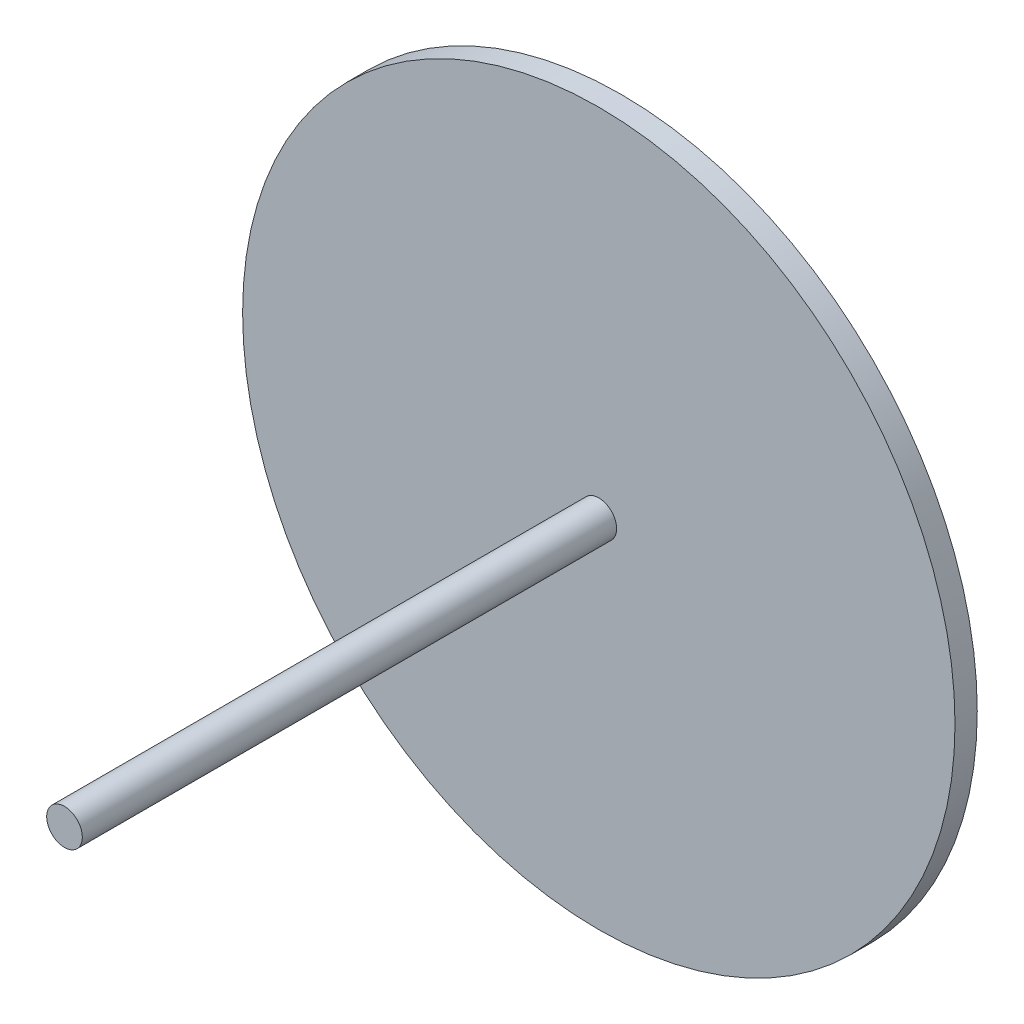
SolidWorks part; units mm, degrees
ref_plane "前视基准面" through (0, 0, 0) normal (0, 0, 1) x (1, 0, 0)
ref_plane "上视基准面" through (0, 0, 0) normal (0, 1, 0) x (1, 0, 0)
ref_plane "右视基准面" through (0, 0, 0) normal (1, 0, 0) x (0, 0, -1)
sketch "草图1" plane through (0, 0, 0) normal (0, 0, 1) x (1, 0, 0)
  circle A0 centre (0, 0) radius 40
  dimension "D1" = 80
extrude "凸台-拉伸1" add sketch "草图1" along normal blind 2.5
sketch "草图2" plane through (0, 0, 2.5) normal (0, 0, 1) x (1, 0, 0)
  circle A0 centre (0, 0) radius 2
  dimension "D1" = 4
extrude "凸台-拉伸2" add sketch "草图2" along normal blind 60
